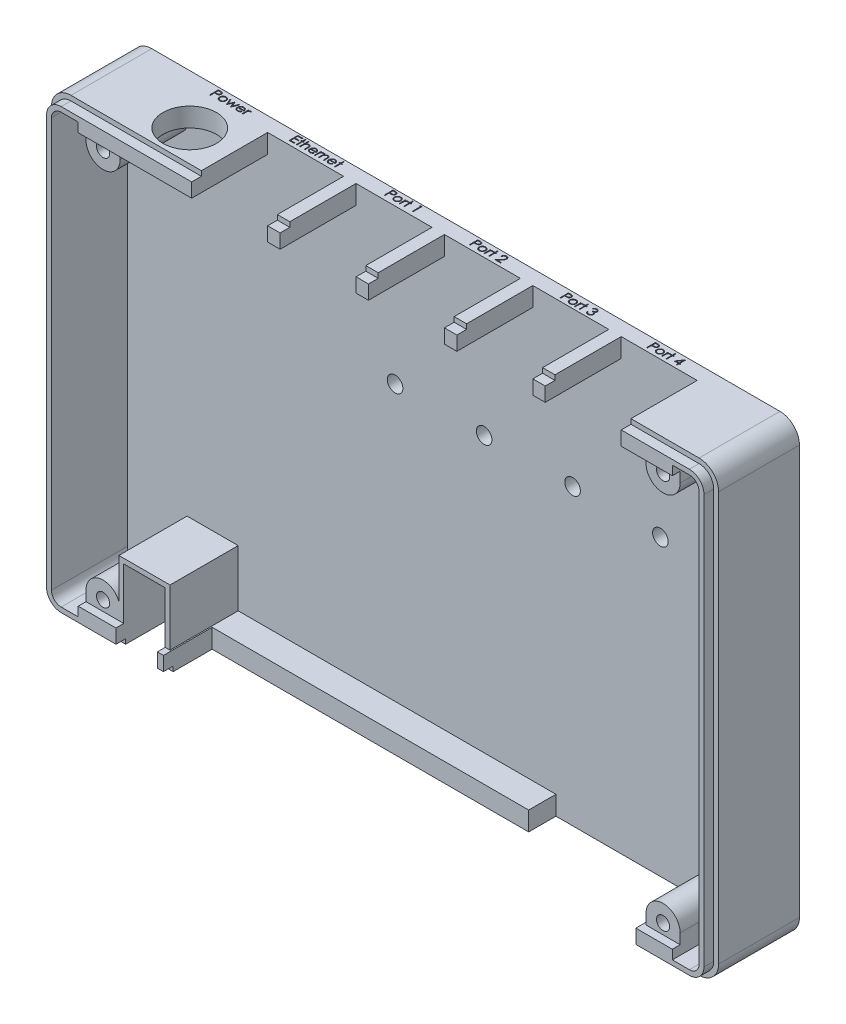
SolidWorks part; units mm, degrees
ref_plane "Front Plane" through (0, 0, 0) normal (0, 0, 1) x (1, 0, 0)
ref_plane "Top Plane" through (0, 0, 0) normal (0, 1, 0) x (1, 0, 0)
ref_plane "Right Plane" through (0, 0, 0) normal (1, 0, 0) x (0, 0, -1)
sketch "Sketch1" plane through (0, 0, 0) normal (0, 0, 1) x (1, 0, 0)
  line L1 (0, 0) -> (137, 0)
  line L2 (0, 0) -> (0, 92)
  line L3 (0, 92) -> (137, 92)
  line L4 (137, 0) -> (137, 92)
  dimension "D1" = 137
  dimension "D2" = 92
extrude "Boss-Extrude1" add sketch "Sketch1" along normal blind 2 and the other way blind 1
sketch "Sketch2" plane through (0, 0, 2) normal (0, 0, 1) x (1, 0, 0)
  line L1 (0, 92) -> (137, 92)
  line L2 (0, 92) -> (0, 0)
  line L3 (0, 0) -> (137, 0)
  line L4 (137, 92) -> (137, 0)
  line L5 (2, 2) -> (135, 2)
  line L6 (2, 2) -> (2, 90)
  line L7 (2, 90) -> (135, 90)
  line L8 (135, 2) -> (135, 90)
  dimension "D1" = 2
  dimension "D2" = 2
  dimension "D3" = 2
  dimension "D4" = 2
extrude "Boss-Extrude2" add sketch "Sketch2" along normal blind 15.6
sketch "Sketch3" plane through (0, 0, 17.6) normal (0, 0, 1) x (1, 0, 0)
  line L1 (0, 0) -> (137, 0)
  line L2 (0, 0) -> (0, 92)
  line L3 (0, 92) -> (137, 92)
  line L4 (137, 0) -> (137, 92)
  line L5 (1, 1) -> (136, 1)
  line L6 (1, 1) -> (1, 91)
  line L7 (1, 91) -> (136, 91)
  line L8 (136, 1) -> (136, 91)
  dimension "D1" = 1
  dimension "D2" = 1
  dimension "D3" = 1
  dimension "D4" = 1
extrude "Boss-Extrude3" add sketch "Sketch3" along normal blind 2
sketch "Sketch4" plane through (0, 0, 2) normal (0, 0, 1) x (1, 0, 0)
  line L0 (0, 0) -> (137, 0) construction
  line L1 (0, 92) -> (0, 0) construction
  line L2 (2, 2) -> (135, 2) construction
  line L4 (7.5, 6) -> (7.5, 2)
  line L5 (7.5, 2) -> (14.5, 2)
  line L6 (14.5, 6) -> (14.5, 2)
  line L7 (137, 0) -> (137, 92) construction
  line L8 (137, 92) -> (0, 92) construction
  line L9 (2, 2) -> (135, 2) construction
  line L11 (122.5, 6) -> (122.5, 2)
  line L12 (122.5, 2) -> (129.5, 2)
  line L13 (129.5, 6) -> (129.5, 2)
  line L14 (135, 90) -> (2, 90) construction
  line L16 (129.5, 86) -> (129.5, 90)
  line L17 (129.5, 90) -> (122.5, 90)
  line L18 (122.5, 86) -> (122.5, 90)
  line L19 (135, 90) -> (2, 90) construction
  line L21 (14.5, 86) -> (14.5, 90)
  line L22 (14.5, 90) -> (7.5, 90)
  line L23 (7.5, 86) -> (7.5, 90)
  arc A0 (14.5, 6) -> (7.5, 6) centre (11, 6) ccw
  circle A1 centre (11, 6) radius 1.35
  arc A2 (7.5, 86) -> (14.5, 86) centre (11, 86) ccw
  circle A3 centre (11, 86) radius 1.35
  arc A4 (122.5, 86) -> (129.5, 86) centre (126, 86) ccw
  circle A5 centre (126, 86) radius 1.35
  arc A6 (129.5, 6) -> (122.5, 6) centre (126, 6) ccw
  circle A7 centre (126, 6) radius 1.35
  dimension "D1" = 2.7
  dimension "D2" = 7
  dimension "D3" = 2.7
  dimension "D4" = 7
  dimension "D5" = 2.7
  dimension "D6" = 7
  dimension "D7" = 2.7
  dimension "D8" = 7
  dimension "D11" = 6
  dimension "D9" = 6
  dimension "D10" = 11
  dimension "D12" = 11
  dimension "D13" = 11
  dimension "D14" = 6
  dimension "D15" = 11
  dimension "D16" = 6
extrude "Boss-Extrude4" add sketch "Sketch4" along normal blind 15.6
sketch "Sketch8" plane through (0, 0, 2) normal (0, 0, 1) x (1, 0, 0)
  line L0 (122.5, 6) -> (122.5, 2) construction
  line L1 (14.5, 2) -> (122.5, 2)
  line L2 (14.5, 2) -> (14.5, 3.9)
  line L3 (14.5, 3.9) -> (122.5, 3.9)
  line L4 (122.5, 2) -> (122.5, 3.9)
  dimension "D1" = 1.9
extrude "Boss-Extrude6" add sketch "Sketch8" along normal blind 15.6
sketch "Sketch11" plane through (0, 0, 2) normal (0, 0, 1) x (1, 0, 0)
  line L0 (122.5, 90) -> (122.5, 86) construction
  line L1 (14.5, 90) -> (122.5, 90)
  line L2 (14.5, 90) -> (14.5, 88.1)
  line L3 (14.5, 88.1) -> (122.5, 88.1)
  line L4 (122.5, 90) -> (122.5, 88.1)
  dimension "D1" = 1.9
extrude "Boss-Extrude7" add sketch "Sketch11" along normal blind 15.6
sketch "Sketch14" plane through (0, 0, 19.6) normal (0, 0, 1) x (1, 0, 0)
  line L1 (0, 92) -> (137, 92)
  line L2 (0, 92) -> (0, 0)
  line L3 (0, 0) -> (137, 0)
  line L4 (137, 92) -> (137, 0)
  line L5 (1, 1) -> (136, 1)
  line L6 (1, 1) -> (1, 91)
  line L7 (1, 91) -> (136, 91)
  line L8 (136, 1) -> (136, 91)
extrude "Cut-Extrude5" cut sketch "Sketch14" against normal blind 4
fillet "Fillet1" radius 2 4 edges at (2, 2, 9.8) (135, 2, 9.8) (135, 90, 9.8) (2, 90, 9.8)
fillet "Fillet3" radius 3 4 edges at (1, 1, 16.6) (136, 1, 16.6) (136, 91, 16.6) (1, 91, 16.6)
fillet "Fillet4" radius 4 4 edges at (0, 92, 7.3) (137, 92, 7.3) (137, 0, 7.3) (0, 0, 7.3)
sketch "Sketch15" plane through (0, 92, 0) normal (0, 1, 0) x (1, 0, 0)
  line L0 (133, -15.6) -> (4, -15.6) construction
  line L1 (0, -15.6) -> (0, 1) construction
  circle A0 centre (22, -9.2) radius 5.5
  dimension "D1" = 11
  dimension "D2" = 6.4
  dimension "D3" = 22
extrude "Cut-Extrude6" cut sketch "Sketch15" against normal blind 4
sketch "Sketch16" plane through (0, 92, 0) normal (0, 1, 0) x (1, 0, 0)
  line L0 (0, -15.6) -> (0, 1) construction
  line L1 (30.8, -17.6) -> (46.4, -17.6)
  line L2 (30.8, -17.6) -> (30.8, -2)
  line L3 (30.8, -2) -> (46.4, -2)
  line L4 (46.4, -17.6) -> (46.4, -2)
  line L5 (133, -17.6) -> (4, -17.6) construction
  dimension "D1" = 30.8
  dimension "D2" = 0
  dimension "D3" = 15.6
  dimension "D4" = 15.6
extrude "Cut-Extrude7" cut sketch "Sketch16" against normal blind 4
sketch "Sketch17" plane through (0, 92, 0) normal (0, 1, 0) x (1, 0, 0)
  line L19 (133, -17.6) -> (46.4, -17.6) construction
  line L20 (48.95, -17.6) -> (64.55, -17.6)
  line L21 (48.95, -17.6) -> (48.95, -2)
  line L22 (48.95, -2) -> (64.55, -2)
  line L23 (64.55, -17.6) -> (64.55, -2)
  line L24 (67.1, -17.6) -> (82.7, -17.6)
  line L25 (67.1, -17.6) -> (67.1, -2)
  line L26 (67.1, -2) -> (82.7, -2)
  line L27 (82.7, -17.6) -> (82.7, -2)
  line L28 (85.25, -17.6) -> (100.85, -17.6)
  line L29 (85.25, -17.6) -> (85.25, -2)
  line L30 (85.25, -2) -> (100.85, -2)
  line L31 (100.85, -17.6) -> (100.85, -2)
  line L32 (103.4, -17.6) -> (119, -17.6)
  line L33 (103.4, -17.6) -> (103.4, -2)
  line L34 (103.4, -2) -> (119, -2)
  line L35 (119, -17.6) -> (119, -2)
  line L36 (0, -15.6) -> (0, 1) construction
  dimension "D1" = 15.6
  dimension "D2" = 15.6
  dimension "D3" = 15.6
  dimension "D4" = 15.6
  dimension "D5" = 15.6
  dimension "D6" = 15.6
  dimension "D7" = 15.6
  dimension "D8" = 15.6
  dimension "D9" = 0
  dimension "D10" = 0
  dimension "D11" = 0
  dimension "D12" = 48.95
  dimension "D13" = 67.1
  dimension "D14" = 85.25
  dimension "D15" = 103.4
  dimension "D16" = 0
extrude "Cut-Extrude8" cut sketch "Sketch17" against normal blind 4
sketch "Sketch19" plane through (0, 0, -1) normal (0, 0, -1) x (-1, 0, 0)
  circle A0 centre (-56.9642, 60.3523) radius 1.6
  circle A1 centre (-75.2522, 60.3523) radius 1.6
  circle A2 centre (-93.4132, 60.3523) radius 1.6
  circle A3 centre (-111.4472, 60.3523) radius 1.6
  dimension "D1" = 3.2
  dimension "D2" = 3.2
  dimension "D3" = 3.2
  dimension "D4" = 3.2
extrude "Cut-Extrude9" cut sketch "Sketch19" against normal blind 4
sketch "Sketch20" plane through (0, 0, 0) normal (0, -1, 0) x (1, 0, 0)
  line L0 (4, 17.6) -> (133, 17.6) construction
  line L1 (122, 17.6) -> (90, 17.6)
  line L2 (122, 17.6) -> (122, 2)
  line L3 (122, 2) -> (90, 2)
  line L4 (90, 17.6) -> (90, 2)
  line L5 (137, 15.6) -> (137, -1) construction
  dimension "D1" = 32
  dimension "D2" = 15.6
  dimension "D3" = 0
  dimension "D4" = 15
extrude "Cut-Extrude10" cut sketch "Sketch20" against normal blind 4
sketch "Sketch21" plane through (0, 0, 0) normal (0, -1, 0) x (1, 0, 0)
  line L1 (90, 17.6) -> (25, 17.6)
  line L2 (90, 17.6) -> (90, 7.6)
  line L3 (90, 7.6) -> (25, 7.6)
  line L4 (25, 17.6) -> (25, 7.6)
  dimension "D1" = 65
  dimension "D2" = 10
extrude "Cut-Extrude11" cut sketch "Sketch21" against normal blind 4
sketch "Sketch22" plane through (0, 0, 17.6) normal (0, 0, 1) x (1, 0, 0)
  line L1 (122.5, 88.1) -> (130.7778, 88.1)
  line L2 (122.5, 88.1) -> (122.5, 81.9328)
  line L3 (122.5, 81.9328) -> (130.7778, 81.9328)
  line L4 (130.7778, 88.1) -> (130.7778, 81.9328)
extrude "Cut-Extrude12" cut sketch "Sketch22" against normal blind 1.6
sketch "Sketch23" plane through (0, 0, 17.6) normal (0, 0, 1) x (1, 0, 0)
  line L1 (122.5, 3.9) -> (130.3517, 3.9)
  line L2 (122.5, 3.9) -> (122.5, 10.7356)
  line L3 (122.5, 10.7356) -> (130.3517, 10.7356)
  line L4 (130.3517, 3.9) -> (130.3517, 10.7356)
extrude "Cut-Extrude13" cut sketch "Sketch23" against normal blind 1.6
sketch "Sketch24" plane through (0, 0, 17.6) normal (0, 0, 1) x (1, 0, 0)
  line L1 (14.5, 3.9) -> (6.9446, 3.9)
  line L2 (14.5, 3.9) -> (14.5, 10.0585)
  line L3 (14.5, 10.0585) -> (6.9446, 10.0585)
  line L4 (6.9446, 3.9) -> (6.9446, 10.0585)
extrude "Cut-Extrude14" cut sketch "Sketch24" against normal blind 1.6
sketch "Sketch25" plane through (0, 0, 17.6) normal (0, 0, 1) x (1, 0, 0)
  line L1 (14.5, 88.1) -> (6.2877, 88.1)
  line L2 (14.5, 88.1) -> (14.5, 80.2964)
  line L3 (14.5, 80.2964) -> (6.2877, 80.2964)
  line L4 (6.2877, 88.1) -> (6.2877, 80.2964)
extrude "Cut-Extrude15" cut sketch "Sketch25" against normal blind 1.6
sketch "Sketch26" plane through (0, 0, -1) normal (0, 0, -1) x (-1, 0, 0)
  line L0 (-4, 0) -> (-133, 0) construction
  line L1 (0, 88) -> (0, 4) construction
  line L2 (-15.25, 0) -> (-23.75, 0)
  line L3 (-15.25, 0) -> (-15.25, 14.5)
  line L4 (-15.25, 14.5) -> (-23.75, 14.5)
  line L5 (-23.75, 0) -> (-23.75, 14.5)
  dimension "D1" = 8.5
  dimension "D2" = 14.5
  dimension "D3" = 15.25
extrude "Cut-Extrude16" cut sketch "Sketch26" against normal blind 23.6
sketch "Sketch29" plane through (0, 0, 2) normal (0, 0, 1) x (1, 0, 0)
  line L0 (25, 3.9) -> (23.75, 3.9) construction
  line L1 (15.25, 3.9) -> (14.25, 3.9)
  line L2 (24.75, 3.9) -> (23.75, 3.9)
  line L3 (24.75, 3.9) -> (24.75, 15.5)
  line L4 (24.75, 15.5) -> (14.25, 15.5)
  line L5 (14.25, 3.9) -> (14.25, 15.5)
  line L7 (23.75, 3.9) -> (23.75, 14.5)
  line L8 (23.75, 14.5) -> (15.25, 14.5)
  line L9 (15.25, 3.9) -> (15.25, 14.5)
  dimension "D1" = 1
  dimension "D2" = 1
  dimension "D3" = 1
extrude "Boss-Extrude8" add sketch "Sketch29" along normal blind 14
sketch "Sketch30" plane through (0, 92, 0) normal (0, 1, 0) x (1, 0, 0)
  text T0 "Ethernet" font "Century Gothic" height 1.8
extrude "Cut-Extrude17" cut sketch "Sketch30" against normal blind 0.5
sketch "Sketch31" plane through (0, 92, 0) normal (0, 1, 0) x (1, 0, 0)
  text T0 "Port 1" font "Century Gothic" height 1.8
extrude "Cut-Extrude18" cut sketch "Sketch31" against normal blind 0.5
sketch "Sketch32" plane through (0, 92, 0) normal (0, 1, 0) x (1, 0, 0)
  text T0 "Port 2" font "Century Gothic" height 1.8
extrude "Cut-Extrude19" cut sketch "Sketch32" against normal blind 0.5
sketch "Sketch33" plane through (0, 92, 0) normal (0, 1, 0) x (1, 0, 0)
  text T0 "Port 3" font "Century Gothic" height 1.8
extrude "Cut-Extrude20" cut sketch "Sketch33" against normal blind 0.5
sketch "Sketch34" plane through (0, 92, 0) normal (0, 1, 0) x (1, 0, 0)
  text T0 "Port 4" font "Century Gothic" height 1.8
extrude "Cut-Extrude21" cut sketch "Sketch34" against normal blind 0.5
sketch "Sketch35" plane through (0, 92, 0) normal (0, 1, 0) x (1, 0, 0)
  text T0 "Power" font "Century Gothic" height 1.8
extrude "Cut-Extrude22" cut sketch "Sketch35" against normal blind 0.5
